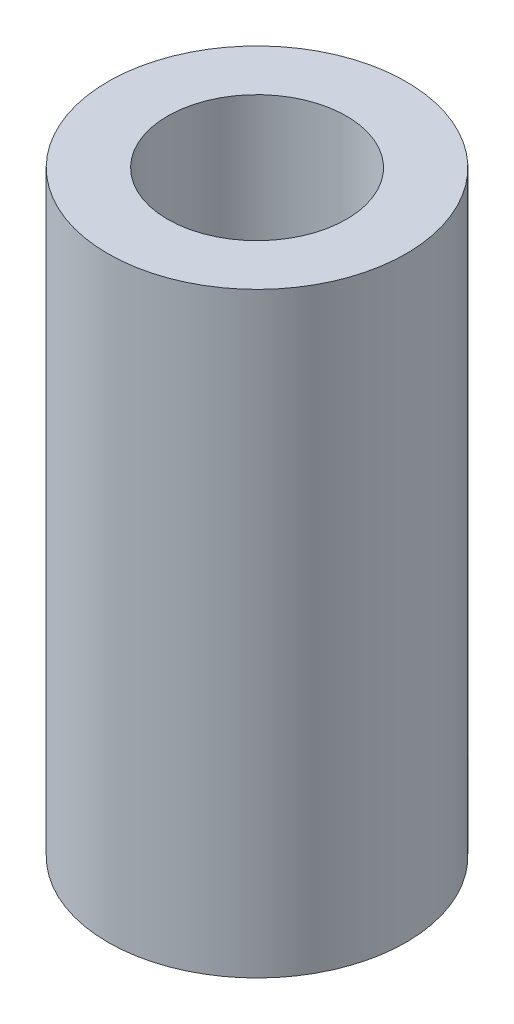
SolidWorks part; units mm, degrees
ref_plane "Front Plane" through (0, 0, 0) normal (0, 0, 1) x (1, 0, 0)
ref_plane "Top Plane" through (0, 0, 0) normal (0, 1, 0) x (1, 0, 0)
ref_plane "Right Plane" through (0, 0, 0) normal (1, 0, 0) x (0, 0, -1)
sketch "Sketch1" plane through (0, 0, 0) normal (0, 1, 0) x (1, 0, 0)
  circle A0 centre (0, 0) radius 2.5
  circle A1 centre (0, 0) radius 1.5
  dimension "D1" = 5
  dimension "D2" = 1
extrude "Boss-Extrude1" add sketch "Sketch1" along normal blind 10
